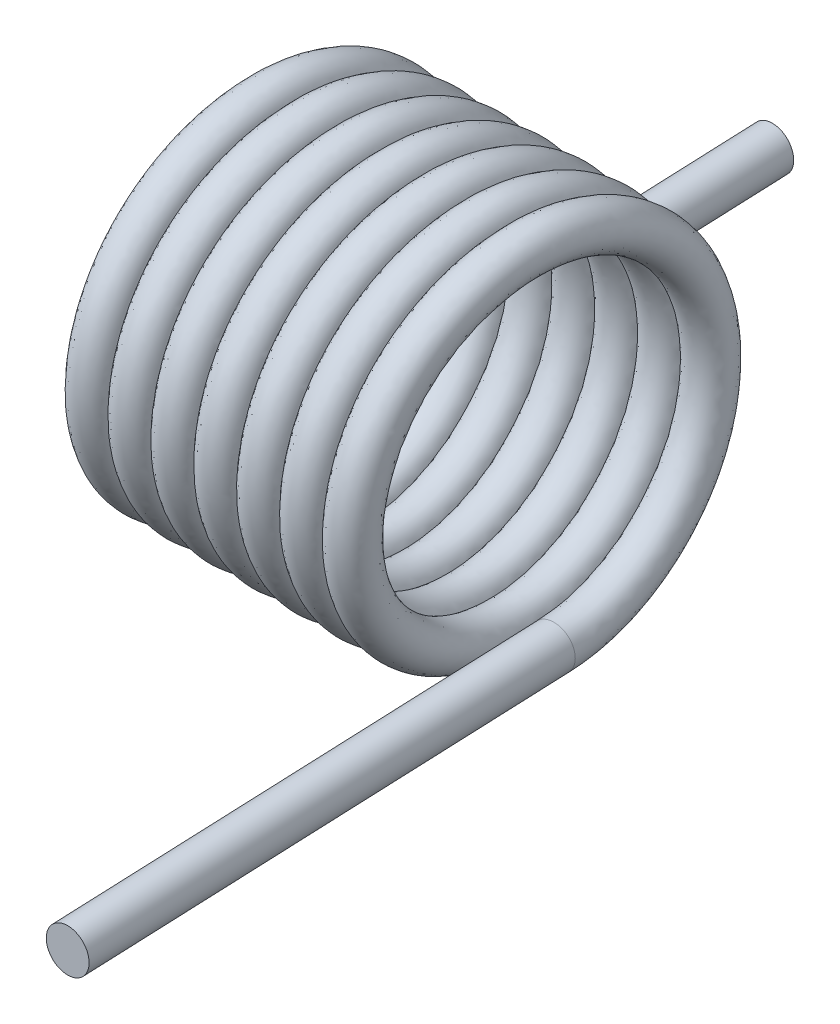
SolidWorks part; units mm, degrees
ref_plane "Front" through (0, 0, 0) normal (0, 0, 1) x (1, 0, 0)
ref_plane "Top" through (0, 0, 0) normal (0, 1, 0) x (1, 0, 0)
ref_plane "Right" through (0, 0, 0) normal (1, 0, 0) x (0, 0, -1)
sketch "Sketch1" plane through (0, 0, 0) normal (1, 0, 0) x (0, 0, -1)
  line L0 (0, 0) -> (0, -1.8288) construction
  line L1 (0, -1.8288) -> (0, -2.0955) construction
  line L2 (0, -2.0955) -> (0, -2.3622) construction
  circle A0 centre (0, 0) radius 1.8288 construction
  circle A1 centre (0, 0) radius 2.3622 construction
  circle A2 centre (0, 0) radius 2.0955
  circle A3 centre (0, -2.0955) radius 0.2667 construction
  circle A4 centre (0, 0) radius 1.3843 construction
curve "Helix/Spiral1" pitch 0.5344 height 3.7408 turns 7
ref_plane "Plane1" through (0, -2.0955, 0) normal (0.0406, 0, 0.9992) x (0.9992, 0, -0.0406)
sketch "Sketch2" plane through (0, -2.0955, 0) normal (0.0406, 0, 0.9992) x (0.9992, 0, -0.0406)
  circle A0 centre (0, 0) radius 0.2667
  dimension "D1" = 0.5334
sweep "Sweep1" add profiles "Sketch2" path "Helix/Spiral1"
sketch "Sketch3" plane through (0, 0, 0) normal (-0.0406, 0, -0.9992) x (-0.9992, 0, 0.0406)
  circle A1 centre (0, -2.0955) radius 0.2667
  circle A2 centre (0, -2.0955) radius 0.2667
  dimension "D1" = 0
extrude "Extrude1" add sketch "Sketch3" along normal blind 19.05
sketch "Sketch4" plane through (0.0062, 0, 0.1516) normal (0.0406, 0, 0.9992) x (0.9955, -0.0856, -0.0404)
  circle A1 centre (3.9034, -1.7678) radius 0.2667
  circle A2 centre (3.9034, -1.7678) radius 0.2667
  dimension "D1" = 0
extrude "Extrude2" add sketch "Sketch4" along normal blind 19.05
sketch "Sketch5" plane through (0, 0, 0) normal (1, 0, 0) x (0, 0, -1)
  circle A0 centre (0, 0) radius 1.3843 construction
  circle A1 centre (0, 0) radius 1.3843
sketch "Sketch6" plane through (0, 0, 0) normal (1, 0, 0) x (0, 0, -1)
  line L0 (19.8993, -1.8288) -> (6.7479, -1.8288)
  line L1 (19.0343, -1.8288) -> (0, -1.8288) construction
  line L2 (6.7479, -1.8288) -> (6.7479, -2.3622)
  line L3 (0, -2.3622) -> (19.0343, -2.3622) construction
  line L4 (6.7479, -2.3622) -> (19.8993, -2.3622)
  line L5 (19.8993, -2.3622) -> (19.8993, -1.8288)
extrude "Cut-Extrude1" cut sketch "Sketch6" against normal blind 2.54
sketch "Sketch7" plane through (0, 0, 0) normal (1, 0, 0) x (0, 0, -1)
  line L0 (-6.3048, -2.3622) -> (-6.3048, -1.8288)
  line L1 (-19.0343, -2.3622) -> (0, -2.3622) construction
  line L2 (0, -1.8288) -> (-19.0343, -1.8288) construction
  line L3 (-6.3048, -1.8288) -> (-19.6214, -1.8288)
  line L4 (-19.6214, -1.8288) -> (-19.6214, -2.3622)
  line L5 (-19.6214, -2.3622) -> (-6.3048, -2.3622)
extrude "Cut-Extrude4" cut sketch "Sketch7" along normal through all both and the other way through all
equation "\"D4@Helix/Spiral1\"=\"Wire Dia@Sketch1\"+.001"
equation "\"D1@Sketch2\"=\"Wire Dia@Sketch1\""
equation "\"D1@Extrude2\"=\"Leg Length@Extrude1\""
